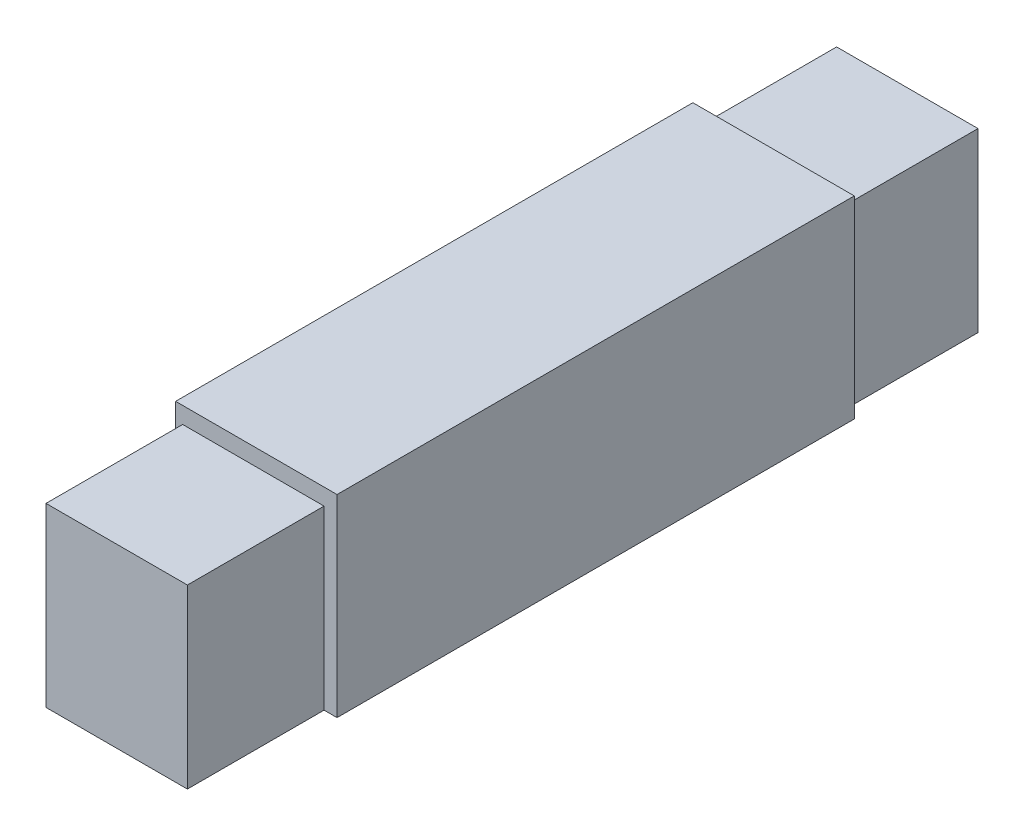
SolidWorks part; units mm, degrees
ref_plane "Front Plane" through (0, 0, 0) normal (0, 0, 1) x (1, 0, 0)
ref_plane "Top Plane" through (0, 0, 0) normal (0, 1, 0) x (1, 0, 0)
ref_plane "Right Plane" through (0, 0, 0) normal (1, 0, 0) x (0, 0, -1)
sketch "Sketch1" plane through (0, 0, 0) normal (0, 0, 1) x (1, 0, 0)
  line L1 (0, 0) -> (34.798, 0)
  line L2 (0, 0) -> (0, 41.656)
  line L3 (0, 41.656) -> (34.798, 41.656)
  line L4 (34.798, 0) -> (34.798, 41.656)
  dimension "D1" = 41.656
  dimension "D2" = 34.798
extrude "Boss-Extrude2" add sketch "Sketch1" along normal blind 111.506 contours L3 L4 L1 L2
sketch "Sketch2" plane through (0, 0, 111.506) normal (0, 0, 1) x (1, 0, 0)
  line L1 (1.524, 0) -> (32.004, 0)
  line L2 (1.524, 0) -> (1.524, 38.1)
  line L3 (1.524, 38.1) -> (32.004, 38.1)
  line L4 (0, 41.656) -> (0, 0)
  line L5 (0, 0) -> (34.798, 0)
  line L6 (34.798, 0) -> (34.798, 41.656)
  line L7 (34.798, 41.656) -> (0, 41.656)
  line L8 (0, 41.656) -> (0, 0)
  line L9 (0, 0) -> (34.798, 0)
  line L10 (34.798, 0) -> (34.798, 41.656)
  line L11 (34.798, 41.656) -> (0, 41.656)
  line L12 (32.004, 0) -> (32.004, 38.1)
  dimension "D2" = 3.556
  dimension "D3" = 1.524
  dimension "D4" = 2.794
  dimension "D1" = 0
extrude "Boss-Extrude3" add sketch "Sketch2" along normal blind 29.464 contours L2 L3 L12 L1
ref_plane "Plane1" through (0, 0, 55.753) normal (0, 0, -1) x (-1, 0, 0)
mirror "Mirror1" about plane through (0, 0, 55.753) normal (0, 0, -1) of "Boss-Extrude3"
